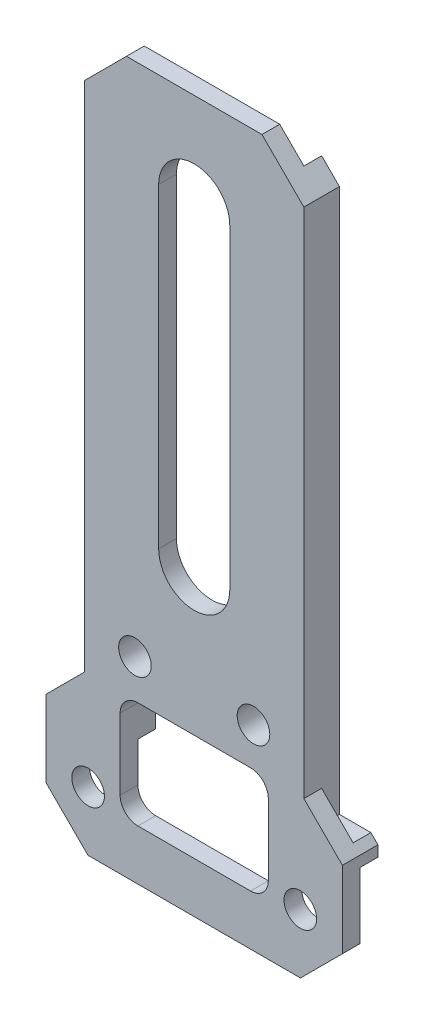
SolidWorks part; units mm, degrees
ref_plane "Front Plane" through (0, 0, 0) normal (0, 0, 1) x (1, 0, 0)
ref_plane "Top Plane" through (0, 0, 0) normal (0, 1, 0) x (1, 0, 0)
ref_plane "Right Plane" through (0, 0, 0) normal (1, 0, 0) x (0, 0, -1)
sketch "Sketch1" plane through (0, 0, 0) normal (0, 0, 1) x (1, 0, 0)
  line L0 (25, 120) -> (25, 0) construction
  line L1 (7.0711, 0) -> (42.9289, 0)
  line L2 (0, 7.0711) -> (0, 20)
  line L3 (13.5711, 120) -> (36.4289, 120)
  line L4 (50, 7.0711) -> (50, 20)
  line L5 (25, 50.75) -> (25, 104) construction
  line L6 (19, 50.75) -> (19, 104)
  line L7 (31, 50.75) -> (31, 104)
  line L8 (0, 10) -> (50, 10) construction
  line L12 (6.5, 112.9289) -> (6.5, 26.5)
  line L13 (6.5, 26.5) -> (0, 20)
  line L14 (43.5, 26.5) -> (50, 20)
  line L15 (43.5, 112.9289) -> (43.5, 26.5)
  line L16 (13.5711, 120) -> (6.5, 112.9289)
  line L17 (36.4289, 120) -> (43.5, 112.9289)
  line L18 (0, 7.0711) -> (7.0711, 0)
  line L19 (50, 7.0711) -> (42.9289, 0)
  line L20 (0, 7.0711) -> (0, 0) construction
  line L21 (12.5, 26.5) -> (37.5, 26.5)
  line L22 (0, 0) -> (7.0711, 0) construction
  line L23 (37.5, 26.5) -> (37.5, 8.5)
  line L24 (37.5, 8.5) -> (12.5, 8.5)
  line L25 (12.5, 26.5) -> (12.5, 8.5)
  arc A0 (19, 50.75) -> (31, 50.75) centre (25, 50.75) ccw
  arc A1 (31, 104) -> (19, 104) centre (25, 104) ccw
  circle A2 centre (7.1, 10) radius 2.75
  circle A3 centre (42.9, 10) radius 2.75
  point P9 (25, 77.375)
  point P39 (25, 26.5)
  point P42 (25, 8.5)
  dimension "D6" = 5.5
  dimension "D10" = 32
  dimension "D3" = 10
  dimension "D1" = 50
  dimension "D2" = 120
  dimension "D4" = 12
  dimension "D5" = 35.8
  dimension "D7" = 10
  dimension "D8" = 18
  dimension "D9" = 8.5
  dimension "D11" = 135
  dimension "D12" = 20
  dimension "D13" = 37
  dimension "D14" = 135
  dimension "D15" = 10
  dimension "D16" = 135
  dimension "D17" = 10
  dimension "D18" = 25
extrude "Boss-Extrude1" add sketch "Sketch1" along normal blind 3
sketch "Sketch3" plane through (0, 0, 3) normal (0, 0, 1) x (1, 0, 0)
  line L0 (25, 44.75) -> (25, 14) construction
  circle A0 centre (15, 33) radius 2.75
  arc A1 (19, 50.75) -> (31, 50.75) centre (25, 50.75) ccw construction
  circle A2 centre (35, 33) radius 2.75
  circle A3 centre (7.1, 10) radius 2.75 construction
  point P13 (25, 14)
  dimension "D1" = 5.5
  dimension "D2" = 23
  dimension "D3" = 20
extrude "Cut-Extrude1" cut sketch "Sketch3" against normal up to next
sketch "Sketch2" plane through (0, 0, 0) normal (0, 0, -1) x (-1, 0, 0)
  line L0 (-50, 18.19) -> (-37.5, 18.19)
  line L1 (-50, 7.0711) -> (-50, 20) construction
  line L2 (0, 20) -> (0, 7.0711) construction
  line L3 (-48.81, 21.19) -> (-43.5, 21.19)
  line L4 (-50, 20) -> (-43.5, 26.5) construction
  line L5 (-6.5, 26.5) -> (0, 20) construction
  line L6 (-48.81, 21.19) -> (-50, 20)
  line L7 (-50, 20) -> (-50, 18.19)
  line L8 (-1.19, 21.19) -> (0, 20)
  line L9 (0, 20) -> (0, 18.19)
  line L10 (-7.0711, 0) -> (-42.9289, 0) construction
  line L11 (-6.5, 112.9289) -> (-6.5, 21.19)
  line L12 (-9.5, 115.9289) -> (-9.5, 38.19)
  line L13 (-13.5711, 120) -> (-6.5, 112.9289) construction
  line L14 (-6.5, 112.9289) -> (-9.5, 115.9289)
  line L15 (-6.5, 21.19) -> (-1.19, 21.19)
  line L16 (-43.5, 112.9289) -> (-43.5, 21.19)
  line L17 (-40.5, 115.9289) -> (-40.5, 38.19)
  line L18 (-43.5, 112.9289) -> (-36.4289, 120) construction
  line L19 (-40.5, 115.9289) -> (-43.5, 112.9289)
  line L21 (-40.5, 38.19) -> (-9.5, 38.19)
  line L22 (-37.5, 18.19) -> (-37.5, 26.5)
  line L23 (-37.5, 26.5) -> (-12.5, 26.5)
  line L24 (-12.5, 26.5) -> (-12.5, 18.19)
  line L25 (-37.5, 8.5) -> (-37.5, 26.5) construction
  line L26 (-37.5, 26.5) -> (-12.5, 26.5) construction
  line L27 (-12.5, 26.5) -> (-12.5, 8.5) construction
  line L28 (-12.5, 18.19) -> (0, 18.19)
  circle A0 centre (-35, 33) radius 2.75
  circle A1 centre (-15, 33) radius 2.75
  dimension "D5" = 5.5
  dimension "D1" = 3
  dimension "D2" = 18.19
  dimension "D3" = 3
  dimension "D4" = 3
  dimension "D6" = 17
extrude "Boss-Extrude2" add sketch "Sketch2" along normal blind 3
fillet "Fillet1" radius 3 4 edges at (37.5, 8.5, 1.5) (37.5, 26.5, 0) (12.5, 26.5, 0) (12.5, 8.5, 1.5)
